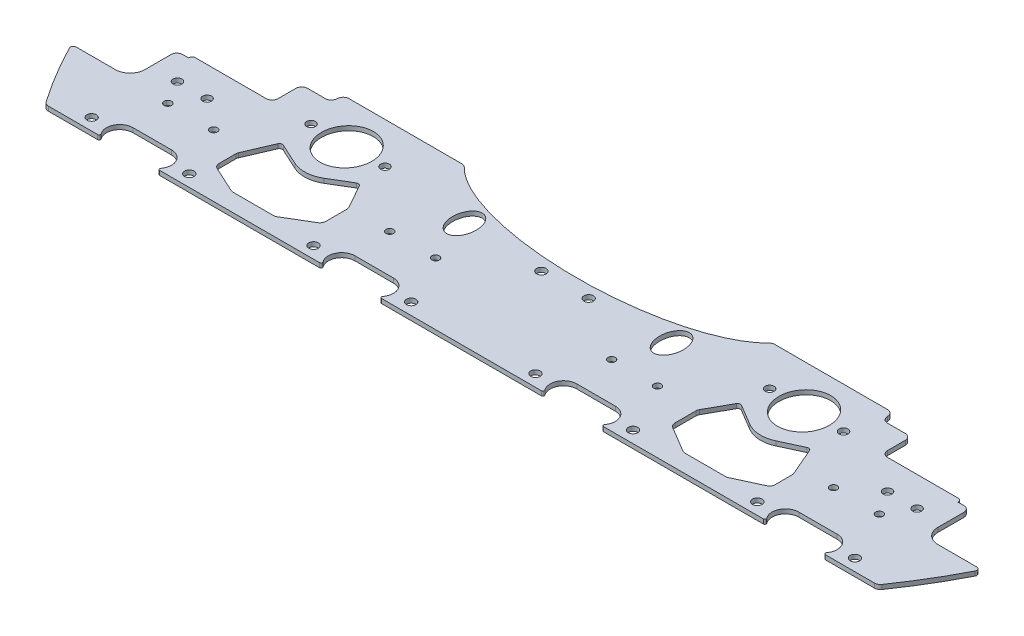
SolidWorks part; units mm, degrees
material "3.3535 (EN-AW 5754)"
ref_plane "Front" through (0, 0, 0) normal (0, 0, 1) x (1, 0, 0)
ref_plane "Top" through (0, 0, 0) normal (0, 1, 0) x (1, 0, 0)
ref_plane "Right" through (0, 0, 0) normal (1, 0, 0) x (0, 0, -1)
sketch "Esquisse1" plane through (0, 0, 0) normal (0, 1, 0) x (1, 0, 0)
  line L1 (0, 55) -> (-134, 55)
  line L2 (0, 55) -> (0, 16)
  line L5 (0, 16) -> (-140.6521, 16)
  line L8 (-153.8018, 38) -> (-134, 38)
  line L9 (-134, 55) -> (-134, 38)
  arc A6 (-153.8018, 38) -> (-140.6521, 16) centre (0, 115) ccw
  dimension "D2" = 99
  dimension "D5" = 60
  dimension "D4" = 172
  dimension "D1" = 55
  dimension "D11" = 17
  dimension "D12" = 134
base flange "Tôle de base pliée1" sketch "Esquisse1" thickness 1.5 reverse thickness direction no parameters "D1"=1
fillet "Congé1" radius 5 1 edges at (-134, -0.75, -38)
sketch "Esquisse2" plane through (0, 0, 0) normal (0, 1, 0) x (1, 0, 0)
  line L1 (0, 55) -> (-103, 55)
  line L2 (0, 55) -> (0, 69)
  line L3 (0, 69) -> (-103, 69)
  line L4 (-103, 55) -> (-103, 69)
  dimension "D1" = 14
  dimension "D2" = 103
base flange "Patte1" sketch "Esquisse2" thickness 1.5 reverse thickness direction no parameters "D1"=1
sketch "Esquisse5" plane through (0, 0, 0) normal (0, 1, 0) x (1, 0, 0)
  line L1 (-120, 55) -> (-120, 45) construction
  line L3 (-103, 55) -> (-134, 55) construction
  line L5 (0, 16) -> (0, 69) construction
  line L9 (-103, 69) -> (-93, 69)
  line L10 (-103, 69) -> (-103, 65)
  line L11 (-103, 65) -> (-93, 65)
  line L12 (-93, 69) -> (-93, 65)
  line L13 (-134, 55) -> (-130, 55)
  line L14 (-134, 55) -> (-134, 53.8)
  line L15 (-134, 53.8) -> (-130, 53.8)
  line L16 (-130, 55) -> (-130, 53.8)
  circle A2 centre (-77.3, 54.5) radius 8.5 construction
  circle A3 centre (-35, 52) radius 4 construction
  circle A4 centre (-125, 45) radius 1.5
  circle A5 centre (-115, 45) radius 1.5
  ellipse E0 centre (-77.3, 54.5) end of major axis (-77.3, 63.5) minor radius 8.5
  ellipse E1 centre (-35, 52) end of major axis (-35, 46) minor radius 4
  dimension "D3" = 77.3
  dimension "D4" = 54.5
  dimension "D2" = 8
  dimension "D5" = 52
  dimension "D6" = 35
  dimension "D11" = 17
  dimension "D14" = 3
  dimension "D15" = 10
  dimension "D17" = 10
  dimension "D7" = 93
  dimension "D8" = 4
  dimension "D10" = 1.2
  dimension "D12" = 18
  dimension "D13" = 12
  dimension "D16" = 120
  dimension "D18" = 10
extrude "Enlèv. mat.-Extru.1" cut sketch "Esquisse5" against normal blind 1.5
sketch "Esquisse7" plane through (0, -1.5, 0) normal (0, -1, 0) x (1, 0, 0)
  line L2 (-94, -26.7769) -> (-94, -34.1277)
  line L4 (-59, -27.9985) -> (-59, -36.744)
  line L5 (0, -16) -> (0, -69) construction
  line L6 (-90.7673, -41.1383) -> (-89.5056, -44.0721)
  line L7 (-90.7673, -41.1383) -> (-89.5056, -44.0721) construction
  line L8 (-88.9775, -44.282) -> (-81.4864, -40.8291)
  line L9 (-88.9775, -44.282) -> (-81.4864, -40.8291) construction
  line L10 (-71.7327, -41.3583) -> (-64.6313, -45.6029)
  line L11 (-71.7327, -41.3583) -> (-64.6313, -45.6029) construction
  line L12 (-64.0849, -45.4513) -> (-62.5339, -42.6702)
  line L13 (-64.0849, -45.4513) -> (-62.5339, -42.6702) construction
  line L14 (-94, -34.1277) -> (-89.4456, -44.7179)
  line L15 (-89.4456, -44.7179) -> (-81.2811, -40.9546)
  line L16 (-71.9645, -41.4527) -> (-64.2106, -46.0874)
  line L17 (-64.2106, -46.0874) -> (-59, -36.744)
  line L18 (-94, -26.7769) -> (-83.6366, -22)
  line L19 (-69.0357, -22) -> (-59, -27.9985)
  line L21 (-83.6366, -22) -> (-69.0357, -22)
  line L22 (-140.6521, -16) -> (0, -16) construction
  arc A0 (-81.2811, -40.9546) -> (-71.9645, -41.4527) centre (-77.095, -50.0363) cw
  dimension "D7" = 10
  dimension "D8" = 6
  dimension "D1" = 94
  dimension "D2" = 59
  dimension "D3" = 0.2
  dimension "D4" = 0.2
  dimension "D5" = 0.2
  dimension "D6" = 0.2
  dimension "D9" = 18
  dimension "D10" = 18
extrude "Enlèv. mat.-Extru.3" cut sketch "Esquisse7" against normal through all
fillet "Congé2" radius 1 4 edges at (-153.8018, -0.75, -38) (-130, -0.75, -55) (-64.2106, -0.75, -46.0874) (-89.4456, -0.75, -44.7179)
fillet "Congé3" radius 2 12 edges at (-134, -0.75, -53.8) (-93, -0.75, -69) (-93, -0.75, -65) (-103, -0.75, -65) (-103, -0.75, -55) (-140.6521, -0.75, -16) (-59, -0.75, -36.744) (-59, -0.75, -27.9985) (-69.0357, -0.75, -22) (-83.6366, -0.75, -22) (-94, -0.75, -26.7769) (-94, -0.75, -34.1277)
sketch "Esquisse6" plane through (0, 0, 0) normal (0, 1, 0) x (1, 0, 0)
  line L0 (-120.25, 37) -> (-104.75, 37) construction
  line L1 (-119, 19.5) -> (-106, 19.5) construction
  line L2 (-119, 24) -> (-106, 24)
  line L3 (-119, 15) -> (-106, 15)
  line L4 (-45.25, 37) -> (-29.75, 37) construction
  line L5 (-139.6102, 16) -> (0, 16) construction
  line L6 (0, 16) -> (0, 69) construction
  line L7 (-105, 55) -> (-129, 55) construction
  line L8 (-44, 19.5) -> (-31, 19.5) construction
  line L9 (-44, 24) -> (-31, 24)
  line L10 (-44, 15) -> (-31, 15)
  line L11 (-139.6102, 16) -> (0, 16) construction
  circle A0 centre (-120.25, 37) radius 1.25
  circle A1 centre (-104.75, 37) radius 1.25
  circle A8 centre (-45.25, 37) radius 1.25
  circle A9 centre (-29.75, 37) radius 1.25
  circle A12 centre (-90, 55.15) radius 1.5
  circle A13 centre (-65, 55.15) radius 1.5
  arc A14 (-119, 24) -> (-119, 15) centre (-119, 19.5) ccw
  arc A15 (-106, 15) -> (-106, 24) centre (-106, 19.5) ccw
  arc A16 (-44, 24) -> (-44, 15) centre (-44, 19.5) ccw
  arc A17 (-31, 15) -> (-31, 24) centre (-31, 19.5) ccw
  point P12 (-112.5, 37)
  point P18 (-37.5, 37)
  point P23 (-112.5, 19.5)
  point P28 (-37.5, 19.5)
  dimension "D1" = 15.5
  dimension "D3" = 2.5
  dimension "D5" = 75
  dimension "D6" = 90
  dimension "D7" = 65
  dimension "D8" = 3
  dimension "D9" = 0.15
  dimension "D12" = 22
  dimension "D2" = 21
  dimension "D4" = 112.5
  dimension "D10" = 1
  dimension "D11" = 13
extrude "Enlèv. mat.-Extru.2" cut sketch "Esquisse6" against normal blind 1.5
fillet "Congé5" radius 0.5 4 edges at (-46.8284, -0.75, -16) (-28.1716, -0.75, -16) (-103.1716, -0.75, -16) (-121.8284, -0.75, -16)
mirror "Symétrie1"
sketch "Esquisse11" plane through (0, 0, 0) normal (0, 1, 0) x (1, 0, 0)
  line L0 (91, 69) -> (-91, 69) construction
  line L1 (-105, 55) -> (-129, 55) construction
  line L2 (0, -50) -> (0, 50) construction
  line L3 (-139.6102, 16) -> (-123, 16) construction
  circle A0 centre (-8, 51) radius 1.6
  circle A1 centre (8, 51) radius 1.6
  circle A2 centre (-129, 20) radius 1.6
  circle A3 centre (-21, 20) radius 1.6
  circle A4 centre (21, 20) radius 1.6
  circle A5 centre (129, 20) radius 1.6
  circle A6 centre (-96, 20) radius 1.6
  circle A7 centre (-54, 20) radius 1.6
  circle A8 centre (54, 20) radius 1.6
  circle A9 centre (96, 20) radius 1.6
  circle A10 centre (-104.75, 37) radius 1.25 construction
  circle A11 centre (-45.25, 37) radius 1.25 construction
  circle A12 centre (-29.75, 37) radius 1.25 construction
  ellipse E0 centre (0, 75) end of major axis (54.5108, 75) minor radius 20
  point P7 (-52, 69)
  dimension "D4" = 3.2
  dimension "D5" = 16
  dimension "D6" = 4
  dimension "D7" = 3.2
  dimension "D8" = 8.75
  dimension "D9" = 129
  dimension "D10" = 4
  dimension "D11" = 42
  dimension "D12" = 8.75
  dimension "D13" = 42
  dimension "D14" = 33
  dimension "D15" = 33
  dimension "D16" = 8.75
  dimension "D1" = 55
  dimension "D2" = 20
  dimension "D3" = 52
extrude "Enlèv. mat.-Extru.4" cut sketch "Esquisse11" against normal through all
fillet "Congé4" radius 2 2 edges at (52, -0.75, -69) (-52, -0.75, -69)
sketch "Lignes de pliage1" [suppressed] plane through (0, 0, 0) normal (0, 1, 0) x (1, 0, 0)
sketch "Cube de visualisation1" [suppressed] plane through (0, 0, 0) normal (0, 1, 0) x (1, 0, 0)
sheet metal parameters "Tôlerie1" thickness 1.5 parameters "D1"=1
flat pattern "Etat déplié1" [suppressed]
sketch "Lignes de pliage2" plane through (0, 0, 0) normal (0, 1, 0) x (1, 0, 0)
sketch3d "Cube de visualisation2" [suppressed]
  line L0 (-153.7837, -3.9999, 0) -> (0, -4, 0) construction
  line L1 (-153.7837, 38.4244, 0) -> (0, 38.4243, 0) construction
  line L2 (-153.7837, -3.9999, 0) -> (-153.7837, 38.4244, 0) construction
  line L3 (0, -4, 0) -> (0, 38.4243, 0) construction
sheet metal parameters "Tôlerie2" thickness 1.5 parameters "D1"=1
flat pattern "Etat déplié2"
sketch "Lignes de pliage3" plane through (0, 0, 0) normal (0, 1, 0) x (1, 0, 0)
sketch3d "Cube de visualisation3" [suppressed]
  line L0 (-153.7837, -3.9999, 0) -> (0, -4, 0) construction
  line L1 (-153.7837, 52.4244, 0) -> (0, 52.4244, 0) construction
  line L2 (-153.7837, -3.9999, 0) -> (-153.7837, 52.4244, 0) construction
  line L3 (0, -4, 0) -> (0, 52.4244, 0) construction
sheet metal parameters "Tôlerie3" thickness 1.5 parameters "D1"=1
flat pattern "Etat déplié2"
sketch "Lignes de pliage3" plane through (0, 0, 0) normal (0, 1, 0) x (1, 0, 0)
sketch3d "Cube de visualisation3" [suppressed]
  line L0 (0, -99, 0) -> (-153.8018, -99, 0) construction
  line L1 (0, -46, 0) -> (-153.8018, -46, 0) construction
  line L2 (0, -99, 0) -> (0, -46, 0) construction
  line L3 (-153.8018, -99, 0) -> (-153.8018, -46, 0) construction
sheet metal parameters "Tôlerie4" thickness 1.5 parameters "D1"=1
flat pattern "Etat déplié4"
sketch "Lignes de pliage4" plane through (0, 0, 0) normal (0, 1, 0) x (1, 0, 0)
sketch3d "Cube de visualisation4" [suppressed]
  line L0 (-153.1738, -99, 0) -> (153.1738, -99, 0) construction
  line L1 (-153.1738, -46, 0) -> (153.1738, -46, 0) construction
  line L2 (-153.1738, -99, 0) -> (-153.1738, -46, 0) construction
  line L3 (153.1738, -99, 0) -> (153.1738, -46, 0) construction
sheet metal parameters "Tôlerie5" thickness 1.5 parameters "D1"=1
flat pattern "Etat déplié2"
sketch "Lignes de pliage3" plane through (0, 0, 0) normal (0, 1, 0) x (1, 0, 0)
sketch3d "Cube de visualisation3" [suppressed]
  line L0 (-153.1738, -99, 0) -> (0, -99, 0) construction
  line L1 (-153.1738, -46, 0) -> (0, -46, 0) construction
  line L2 (-153.1738, -99, 0) -> (-153.1738, -46, 0) construction
  line L3 (0, -99, 0) -> (0, -46, 0) construction
sheet metal parameters "Tôlerie6" thickness 1.5 parameters "D1"=1
flat pattern "Etat déplié2"
sketch "Lignes de pliage3" plane through (0, 0, 0) normal (0, 1, 0) x (1, 0, 0)
sketch3d "Cube de visualisation3" [suppressed]
  line L0 (-153.1738, -99, 0) -> (0, -99, 0) construction
  line L1 (-153.1738, -46, 0) -> (0, -46, 0) construction
  line L2 (-153.1738, -99, 0) -> (-153.1738, -46, 0) construction
  line L3 (0, -99, 0) -> (0, -46, 0) construction
sheet metal parameters "Tôlerie8" thickness 1.5 parameters "D1"=1
flat pattern "Etat déplié4"
sketch "Lignes de pliage4" plane through (0, 0, 0) normal (0, 1, 0) x (1, 0, 0)
sketch3d "Cube de visualisation4" [suppressed]
  line L0 (-153.1738, -99, 0) -> (153.1738, -99, 0) construction
  line L1 (-153.1738, -46, 0) -> (153.1738, -46, 0) construction
  line L2 (-153.1738, -99, 0) -> (-153.1738, -46, 0) construction
  line L3 (153.1738, -99, 0) -> (153.1738, -46, 0) construction
